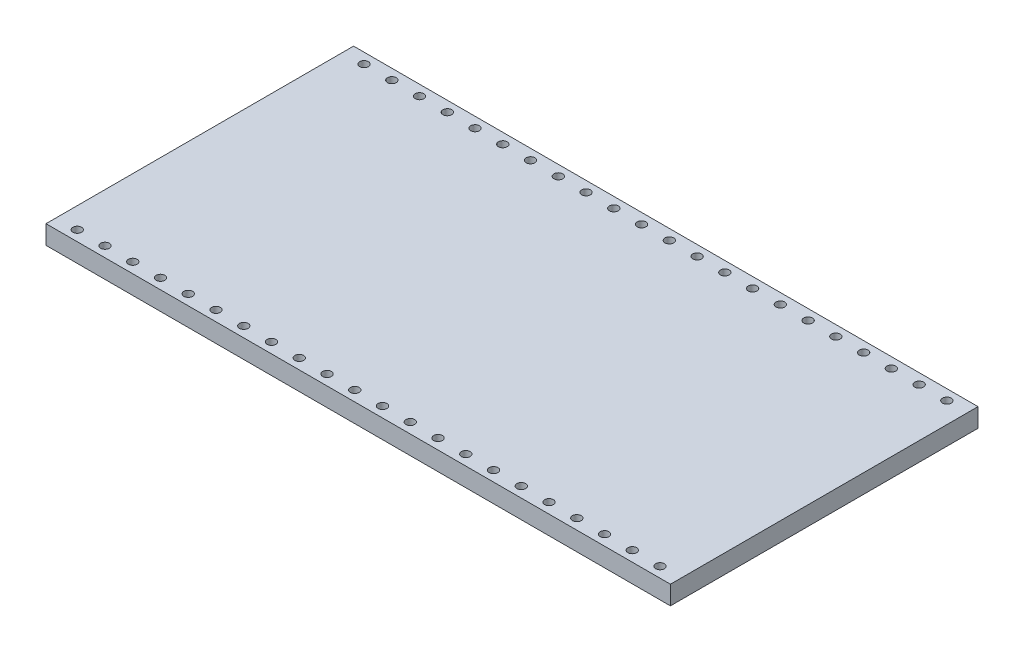
SolidWorks part; units mm, degrees
ref_plane "Front Plane" through (0, 0, 0) normal (0, 0, 1) x (1, 0, 0)
ref_plane "Top Plane" through (0, 0, 0) normal (0, 1, 0) x (1, 0, 0)
ref_plane "Right Plane" through (0, 0, 0) normal (1, 0, 0) x (0, 0, -1)
sketch "Sketch1" plane through (0, 0, 0) normal (0, 1, 0) x (1, 0, 0)
  line L1 (-28.575, -14.075) -> (28.575, -14.075)
  line L2 (-28.575, -14.075) -> (-28.575, 14.075)
  line L3 (-28.575, 14.075) -> (28.575, 14.075)
  line L4 (28.575, -14.075) -> (28.575, 14.075)
  line L5 (-28.575, -14.075) -> (28.575, 14.075) construction
  line L6 (-28.575, 14.075) -> (28.575, -14.075) construction
  point P0 (0, 0)
  dimension "D1" = 28.15
  dimension "D2" = 57.15
extrude "Boss-Extrude1" add sketch "Sketch1" along normal blind 1.72
sketch "Sketch2" plane through (0, 1.72, 0) normal (0, 1, 0) x (1, 0, 0)
  line L0 (28.575, 14.075) -> (-28.575, 14.075) construction
  line L1 (28.575, -14.075) -> (28.575, 14.075) construction
  circle A0 centre (26.675, 13.125) radius 0.4
  dimension "D1" = 0.8
  dimension "D2" = 0.95
  dimension "D3" = 1.9
extrude "Cut-Extrude1" cut sketch "Sketch2" against normal through all
pattern_linear "LPattern1" count 22 spacing 2.54 along (-1, 0, 0) of "Cut-Extrude1"
mirror "Mirror1" about plane through (0, 0, 0) normal (0, 0, 1) of "LPattern1"
